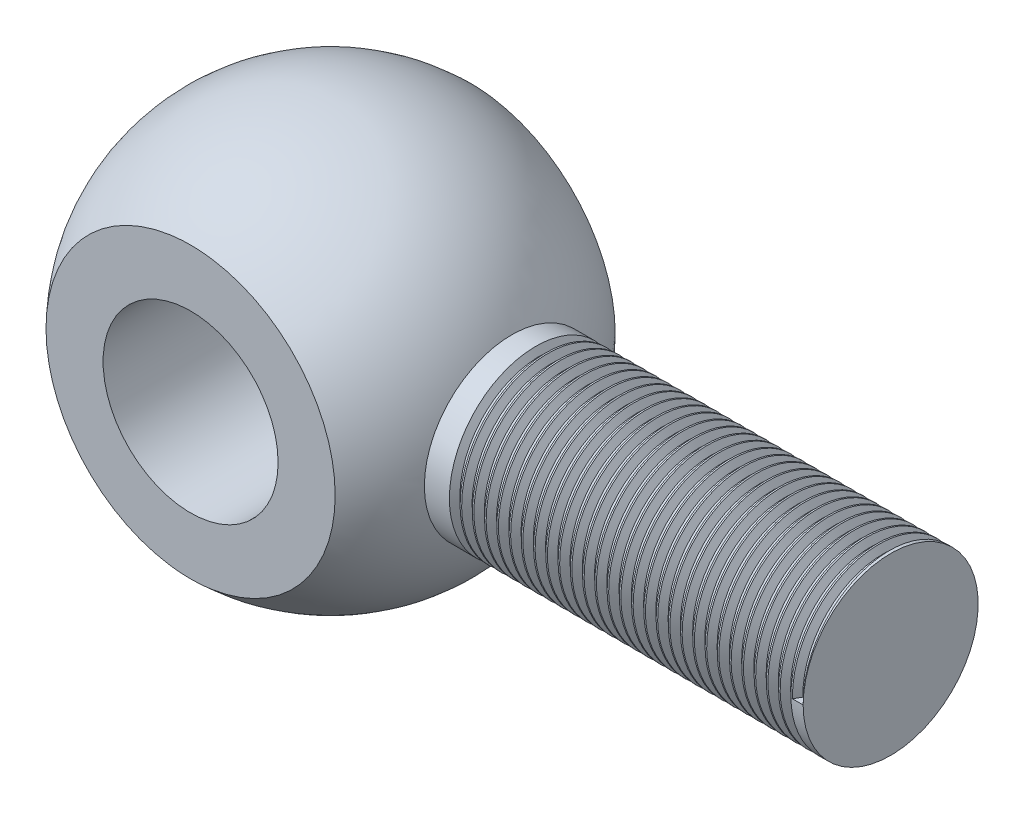
SolidWorks part; units mm, degrees
ref_plane "Front Plane" through (0, 0, 0) normal (0, 0, 1) x (1, 0, 0)
ref_plane "Top Plane" through (0, 0, 0) normal (0, 1, 0) x (1, 0, 0)
ref_plane "Right Plane" through (0, 0, 0) normal (1, 0, 0) x (0, 0, -1)
sketch "Sketch1" plane through (0, 0, 0) normal (0, 0, 1) x (1, 0, 0)
  line L0 (0, 0) -> (0, 11.5)
  arc A0 (0, 11.5) -> (0, 0) centre (0, 5.75) cw
revolve "Revolve1" add sketch "Sketch1" angle 360 about L0
sketch "Sketch2" plane through (0, 0, 0) normal (0, 0, 1) x (1, 0, 0)
  circle A0 centre (0, 5.75) radius 2.5
extrude "Cut-Extrude2" cut sketch "Sketch2" against normal through all both and the other way through all
ref_plane "Plane1" through (0, 0, 6) normal (0, 0, 1) x (1, 0, 0)
sketch "Sketch3" plane through (0, 0, 6) normal (0, 0, 1) x (1, 0, 0)
  line L1 (-5.75, 11.5) -> (5.75, 11.5)
  line L2 (-5.75, 11.5) -> (-5.75, 0)
  line L3 (-5.75, 0) -> (5.75, 0)
  line L4 (5.75, 11.5) -> (5.75, 0)
extrude "Cut-Extrude3" cut sketch "Sketch3" against normal blind 2
ref_plane "Plane2" through (0, 0, -6) normal (0, 0, 1) x (1, 0, 0)
sketch "Sketch4" plane through (0, 0, -6) normal (0, 0, 1) x (1, 0, 0)
  line L1 (-5.75, 11.5) -> (5.75, 11.5)
  line L2 (-5.75, 11.5) -> (-5.75, 0)
  line L3 (-5.75, 0) -> (5.75, 0)
  line L4 (5.75, 11.5) -> (5.75, 0)
extrude "Cut-Extrude4" cut sketch "Sketch4" along normal blind 2
ref_plane "Plane3" through (6, 0, 0) normal (1, 0, 0) x (0, 0, -1)
sketch "Sketch5" plane through (6, 0, 0) normal (1, 0, 0) x (0, 0, -1)
  circle A0 centre (0, 5.75) radius 2.5
extrude "Boss-Extrude1" add sketch "Sketch5" along normal blind 10 and the other way up to surface other way up to face at (4.1307, 5.75, -4)
thread "Thread1" pitch 0.35 method cut profile "Thread Profile2" start angle 0, offset 0, length 10, pitch 0.35, diameter 5
ref_plane "Plane5" through (16, 5.75, 2.5) normal (0, -1, 0) x (0, 0, 1)
sketch "Thread Profile2" plane through (16, 5.75, 2.5) normal (0, -1, 0) x (0, 0, 1)
  line L0 (0, 0) -> (0, 0.35) construction
  line L11 (0, 0) -> (0, 0.3062)
  line L12 (0, 0.3062) -> (-0.1894, 0.1969)
  line L13 (-0.1894, 0.1969) -> (-0.1894, 0.1094)
  line L15 (-0.1894, 0.1094) -> (0, 0)
  line L17 (-0.1894, 0.1531) -> (0, 0.1531) construction
  point P2 (0, 0)
  dimension "Pitch" = 0.35
  dimension "Profile_Angle" = 60
  dimension "Profile_Land" = 0.0875
  dimension "Profile_Height" = 0.1894
